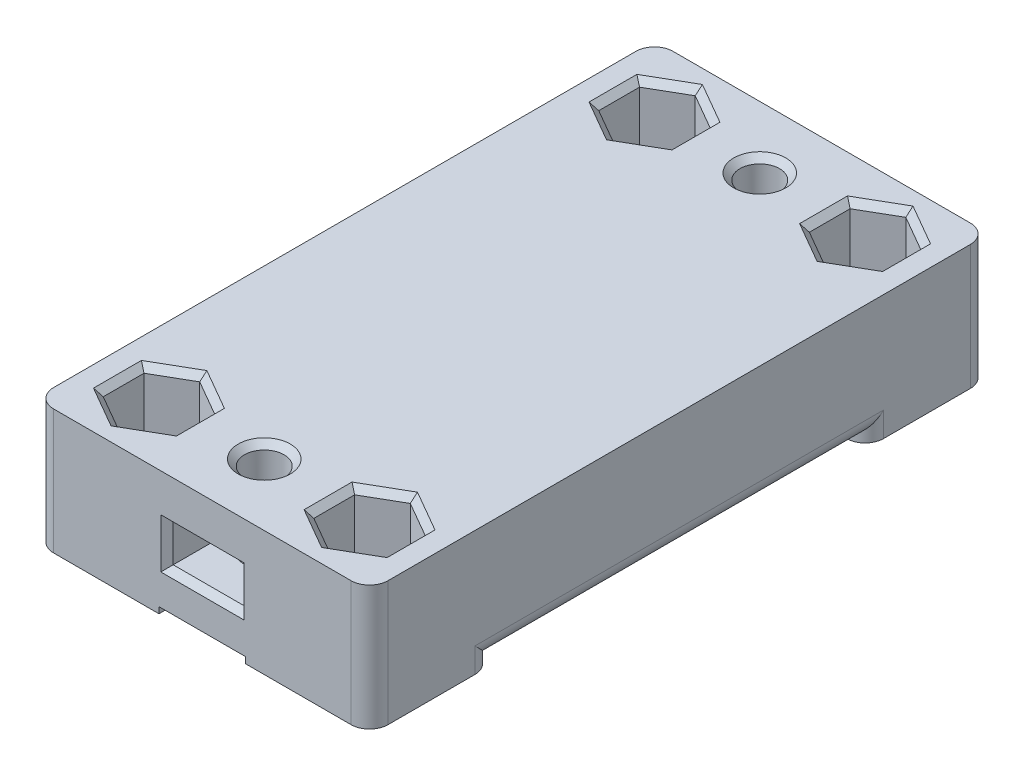
SolidWorks part; units mm, degrees
ref_plane "Спереди" through (0, 0, 0) normal (0, 0, 1) x (1, 0, 0)
ref_plane "Сверху" through (0, 0, 0) normal (0, 1, 0) x (1, 0, 0)
ref_plane "Справа" through (0, 0, 0) normal (1, 0, 0) x (0, 0, -1)
sketch "Эскиз1" plane through (0, 0, 0) normal (1, 0, 0) x (0, 0, -1)
  line L0 (-4.6849, 0) -> (3.7102, 0) construction
  line L1 (0, 4.9836) -> (0, -4.0089) construction
  line L2 (-25, 6.43) -> (25, 6.43)
  line L3 (-25, 6.43) -> (-25, 16)
  line L4 (-25, 16) -> (25, 16)
  line L5 (25, 16) -> (25, 6.43)
  point P7 (0, 6.43)
  dimension "D1" = 6.43
  dimension "D2" = 50
  dimension "D3" = 16
extrude "Бобышка-Вытянуть1" add sketch "Эскиз1" along normal mid plane 27
sketch "Эскиз2" plane through (0, 16, 0) normal (0, 1, 0) x (1, 0, 0)
  line L0 (13.5, 25) -> (13.5, -25) construction
  line L1 (-8.5, 20) -> (8.5, 20) construction
  line L2 (-8.5, 20) -> (-8.5, -20) construction
  line L3 (-8.5, -20) -> (8.5, -20) construction
  line L4 (8.5, 20) -> (8.5, -20) construction
  line L5 (-8.5, 20) -> (8.5, -20) construction
  line L6 (-8.5, -20) -> (8.5, 20) construction
  line L7 (13.5, 25) -> (-13.5, 25) construction
  line L8 (-2.85, 21.6454) -> (-2.85, 25)
  line L9 (-8.5, 16.7091) -> (-5.65, 18.3546)
  line L10 (-5.65, 18.3546) -> (-5.65, 21.6454)
  line L11 (-5.65, 21.6454) -> (-8.5, 23.2909)
  line L12 (-8.5, 23.2909) -> (-11.35, 21.6454)
  line L13 (-11.35, 21.6454) -> (-11.35, 18.3546)
  line L14 (-11.35, 18.3546) -> (-8.5, 16.7091)
  line L15 (0, 16.7091) -> (2.85, 18.3546)
  line L16 (2.85, 18.3546) -> (2.85, 21.6454)
  line L17 (2.85, 21.6454) -> (0, 23.2909)
  line L18 (0, 23.2909) -> (-2.85, 21.6454)
  line L19 (-2.85, 21.6454) -> (-2.85, 18.3546)
  line L20 (-2.85, 18.3546) -> (0, 16.7091)
  line L21 (8.5, 16.7091) -> (11.35, 18.3546)
  line L22 (11.35, 18.3546) -> (11.35, 21.6454)
  line L23 (11.35, 21.6454) -> (8.5, 23.2909)
  line L24 (8.5, 23.2909) -> (5.65, 21.6454)
  line L25 (5.65, 21.6454) -> (5.65, 18.3546)
  line L26 (5.65, 18.3546) -> (8.5, 16.7091)
  line L27 (8.5, -23.2909) -> (11.35, -21.6454)
  line L28 (11.35, -21.6454) -> (11.35, -18.3546)
  line L29 (11.35, -18.3546) -> (8.5, -16.7091)
  line L30 (8.5, -16.7091) -> (5.65, -18.3546)
  line L31 (5.65, -18.3546) -> (5.65, -21.6454)
  line L32 (5.65, -21.6454) -> (8.5, -23.2909)
  line L33 (0, -23.2909) -> (2.85, -21.6454)
  line L34 (2.85, -21.6454) -> (2.85, -18.3546)
  line L35 (2.85, -18.3546) -> (0, -16.7091)
  line L36 (0, -16.7091) -> (-2.85, -18.3546)
  line L37 (-2.85, -18.3546) -> (-2.85, -21.6454)
  line L38 (-2.85, -21.6454) -> (0, -23.2909)
  line L39 (-8.5, -16.7091) -> (-11.35, -18.3546)
  line L40 (-11.35, -18.3546) -> (-11.35, -21.6454)
  line L41 (-11.35, -21.6454) -> (-8.5, -23.2909)
  line L42 (-8.5, -23.2909) -> (-5.65, -21.6454)
  line L43 (-5.65, -21.6454) -> (-5.65, -18.3546)
  line L44 (-5.65, -18.3546) -> (-8.5, -16.7091)
  line L45 (-2.85, 25) -> (2.85, 25)
  line L46 (2.85, 25) -> (2.85, 21.6454)
  line L47 (-2.85, -21.6454) -> (-2.85, -25)
  line L48 (13.5, -25) -> (-13.5, -25) construction
  line L49 (-2.85, -25) -> (2.85, -25)
  line L50 (2.85, -25) -> (2.85, -21.6454)
  circle A0 centre (-8.5, 20) radius 1.6
  circle A1 centre (0, 20) radius 1.6
  circle A2 centre (8.5, 20) radius 1.6
  circle A3 centre (8.5, -20) radius 1.6
  circle A4 centre (0, -20) radius 1.6
  circle A5 centre (-8.5, -20) radius 1.6
  circle A6 centre (-8.5, 20) radius 2.85 construction
  circle A7 centre (0, 20) radius 2.85 construction
  circle A8 centre (8.5, 20) radius 2.85 construction
  circle A9 centre (8.5, -20) radius 2.85 construction
  circle A10 centre (0, -20) radius 2.85 construction
  circle A11 centre (-8.5, -20) radius 2.85 construction
  point P0 (0, 0)
  point P10 (0, 20)
  point P11 (0, -20)
  line M6 (-13.5, -25) -> (13.5, -25)
  line M8 (13.5, 25) -> (-13.5, 25)
  dimension "D3" = 3.2
  dimension "D4" = 5.7
  dimension "D1" = 5
  dimension "D2" = 5
extrude "Вырез-Вытянуть1" cut sketch "Эскиз2" against normal blind 4.57 contours L10 L11 L12 L13 L14 L9 | L22 L23 L24 L25 L26 L21 | L28 L29 L30 L31 L32 L27 | L43 L44 L39 L40 L41 L42
extrude "Вырез-Вытянуть2" cut sketch "Эскиз2<3>" along normal blind 3 from offset 6.57 contours A1 | L19 L20 L15 L16 L17 L18 A1 | L46 L8 L18 L17 M8 | A4 | L37 L38 L33 L34 L35 L36 A4 | L50 L33 L38 L47 M6 region at (0, 16, -23.6895) region at (-1.3815, 16, -22.3928) region at (-1.3815, 16, 22.3928) region at (0, 16, 23.6895) region at (0, 16, -20) region at (0, 16, 20) offset against normal yes
sketch "Эскиз2<3>" plane through (0, 16, 0) normal (0, 1, 0) x (1, 0, 0) same geometry as "Эскиз2"
extrude "Вырез-Вытянуть4" cut sketch "Эскиз2<5>" against normal blind 7.57 contours A4 | A1 region at (0, 16, -20) region at (0, 16, 20)
sketch "Эскиз2<5>" plane through (0, 16, 0) normal (0, 1, 0) x (1, 0, 0) same geometry as "Эскиз2"
sketch "Эскиз3" plane through (0, 6.43, 0) normal (0, -1, 0) x (1, 0, 0)
  line L0 (-29.5221, 15) -> (28.8596, 15) construction
  line L1 (-29.652, -15) -> (35.0939, -15) construction
  line L2 (13.5, -25) -> (-13.5, -25) construction
  line L3 (13.5, 25) -> (-13.5, 25) construction
  line L4 (0, 15) -> (0, -15) construction
  line L6 (-3.5, 15) -> (3.5, 15)
  line L7 (-3.5, 15) -> (-3.5, -15)
  line L8 (-3.5, -15) -> (3.5, -15)
  line L9 (3.5, 15) -> (3.5, -15)
  line L10 (6.5, 15) -> (10.5, 15)
  line L11 (6.5, 15) -> (6.5, -15)
  line L12 (6.5, -15) -> (10.5, -15)
  line L13 (10.5, 15) -> (10.5, -15)
  line L14 (-10.5, 15) -> (-6.5, 15)
  line L15 (-10.5, 15) -> (-10.5, -15)
  line L16 (-10.5, -15) -> (-6.5, -15)
  line L17 (-6.5, 15) -> (-6.5, -15)
  line L18 (13.5, 25) -> (13.5, -25) construction
  line L19 (-13.5, 15) -> (-3.5, 15)
  line L20 (-13.5, 25) -> (-13.5, -25) construction
  line L21 (3.5, 15) -> (13.5, 15) construction
  point P15 (0, 15)
  point P24 (-8.5, 15)
  point P26 (8.5, 15)
  point P28 (8.5, 15)
  point P31 (-8.5, 15)
  dimension "D4" = 3
  dimension "D1" = 10
  dimension "D2" = 10
  dimension "D3" = 7
extrude "Вырез-Вытянуть5" cut sketch "Эскиз3" against normal blind 6.57 contours L17 L14 L15 L16 | L9 L6 L7 L8 | L13 L10 L11 L12 region at (0, 6.43, 0) region at (-8.5, 6.43, 0) region at (8.5, 6.43, 0)
sketch "Эскиз4" plane through (0, 6.43, 0) normal (0, -1, 0) x (-1, 0, 0)
  line L0 (3.5, 15) -> (-3.5, 15) construction
  line L1 (13.5, -25) -> (3.5, -25)
  line L2 (13.5, -25) -> (13.5, -15)
  line L3 (13.5, -15) -> (3.5, -15)
  line L4 (3.5, -25) -> (3.5, -15)
  line L5 (-13.5, -25) -> (-3.5, -25)
  line L6 (-13.5, -25) -> (-13.5, -15)
  line L7 (-13.5, -15) -> (-3.5, -15)
  line L8 (-3.5, -25) -> (-3.5, -15)
  line L9 (13.5, 25) -> (3.5, 25)
  line L10 (13.5, 25) -> (13.5, 15)
  line L11 (13.5, 15) -> (3.5, 15)
  line L12 (3.5, 25) -> (3.5, 15)
  line L14 (-13.5, 25) -> (-3.5, 25)
  line L15 (-13.5, 25) -> (-13.5, 15)
  line L16 (-13.5, 15) -> (-3.5, 15)
  line L17 (-3.5, 25) -> (-3.5, 15)
extrude "Бобышка-Вытянуть2" add sketch "Эскиз4" along normal blind 0.5
extrude "Вырез-Вытянуть3" cut sketch "Эскиз2<4>" against normal blind 16 contours A2 | A0 | A3 | A5 region at (-8.5, 16, -20) region at (8.5, 16, -20) region at (8.5, 16, 20) region at (-8.5, 16, 20)
sketch "Эскиз2<4>" plane through (0, 16, 0) normal (0, 1, 0) x (1, 0, 0) same geometry as "Эскиз2"
fillet "Скругление1" radius 1.5 16 edges at (13.5, 10.965, 25) (-13.5, 10.965, 25) (13.5, 10.965, -25) (-13.5, 10.965, -25) (13.5, 6.18, 15) (13.5, 6.18, -15) (-13.5, 6.18, -15) (13.5, 6.43, 0) (10.5, 6.43, 0) (6.5, 6.43, 0) (3.5, 6.43, 0) (-3.5, 6.43, 0)
chamfer "Фаска1" distance 0.5 angle 45 38 edges at (-9.925, 16, -22.4682) (-11.35, 16, -20) (-9.925, 16, -17.5318) (-7.075, 16, -17.5318) (-5.65, 16, -20) (-7.075, 16, -22.4682) (9.925, 16, -17.5318) (11.35, 16, -20) (9.925, 16, -22.4682) (7.075, 16, -22.4682) (5.65, 16, -20) (7.075, 16, -17.5318) (-7.075, 16, 22.4682) (-9.925, 16, 22.4682) (-11.35, 16, 20) (-9.925, 16, 17.5318) (-7.075, 16, 17.5318) (-5.65, 16, 20) (5.65, 16, 20) (7.075, 16, 22.4682) (9.925, 16, 22.4682) (11.35, 16, 20) (9.925, 16, 17.5318) (7.075, 16, 17.5318) (0, 16, 21.6) (0, 16, -18.4) (0, 12.43, -25) (-2.85, 10.93, -25) (0, 9.43, -25) (2.85, 10.93, -25) (-8.5, 5.93, 18.4) (8.5, 5.93, 21.6) (8.5, 5.93, -21.6) (-8.5, 5.93, -18.4) (-2.85, 10.93, 25) (0, 12.43, 25) (2.85, 10.93, 25) (0, 9.43, 25)
